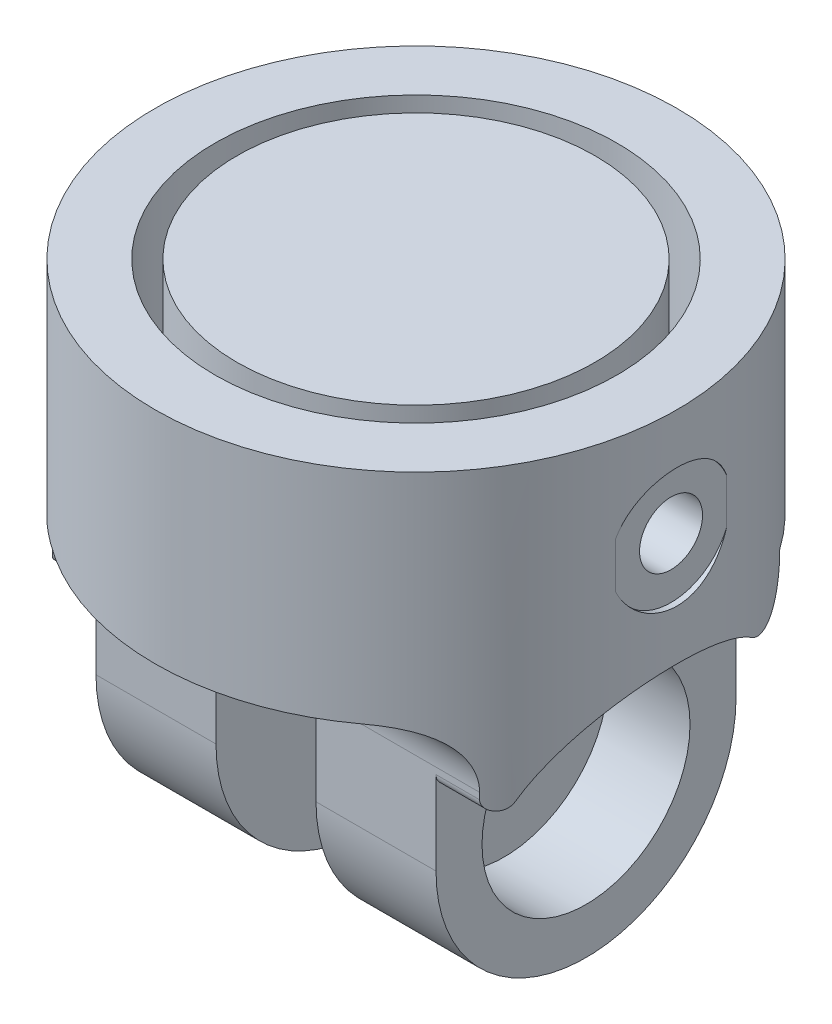
SolidWorks part; units mm, degrees
material "PLA Black"
ref_plane "Front" through (0, 0, 0) normal (0, 0, 1) x (1, 0, 0)
ref_plane "Top" through (0, 0, 0) normal (0, 1, 0) x (1, 0, 0)
ref_plane "Right" through (0, 0, 0) normal (1, 0, 0) x (0, 0, -1)
sketch "Sketch1" plane through (0, 0, 0) normal (0, 1, 0) x (1, 0, 0)
  line L0 (0, 8.95) -> (0, 10.05) construction
  circle A0 centre (0, 0) radius 10.05
  circle A1 centre (0, 0) radius 13.05
  circle A2 centre (0, 0) radius 9.5 construction
  circle A4 centre (0, 0) radius 8.95
  point P11 (0, 9.5)
  dimension "D1" = 1.1
  dimension "D2" = 3
  dimension "D3" = 19
extrude "Boss-Extrude1" add sketch "Sketch1" along normal blind 10 contours A1 A0 | A4 region at (-12.6809, 0, 0) region at (0, 0, 0)
sketch "Sketch3" plane through (0, 0, 0) normal (0, -1, 0) x (1, 0, 0)
  circle A2 centre (0, 0) radius 13.05 construction
  circle A3 centre (0, 0) radius 13.05
extrude "Boss-Extrude2" add sketch "Sketch3" along normal blind 1
sketch "Sketch4" plane through (0, -1, 0) normal (0, -1, 0) x (1, 0, 0)
  line L0 (0, 17.8908) -> (0, -17.0763) construction
  line L1 (2.5, 7.5) -> (8.5, 7.5)
  line L2 (2.5, 7.5) -> (2.5, -7.5)
  line L3 (2.5, -7.5) -> (8.5, -7.5)
  line L4 (8.5, 7.5) -> (8.5, -7.5)
  line L5 (-8.5, 7.5) -> (-8.5, -7.5)
  line L6 (-2.5, -7.5) -> (-8.5, -7.5)
  line L7 (-2.5, 7.5) -> (-2.5, -7.5)
  line L8 (-2.5, 7.5) -> (-8.5, 7.5)
  line L9 (16.8049, 0) -> (-19.8998, 0) construction
  dimension "D1" = 6
  dimension "D2" = 5
  dimension "D3" = 15
extrude "Boss-Extrude3" add sketch "Sketch4" along normal blind 15
sketch "Sketch5" plane through (8.5, 0, 0) normal (1, 0, 0) x (0, 0, -1)
  line L0 (-7.5, -16) -> (-7.5, -1) construction
  line L1 (7.5, -16) -> (7.5, -1) construction
  line L2 (7.5, -8.5) -> (7.5, -17.1619)
  line L3 (7.5, -17.1619) -> (-7.5, -17.1619)
  line L4 (-7.5, -17.1619) -> (-7.5, -8.5)
  arc A0 (-7.5, -8.5) -> (7.5, -8.5) centre (0, -8.5) ccw
  circle A1 centre (0, -8.5) radius 1.55
  dimension "D1" = 3.1
extrude "Cut-Extrude1" cut sketch "Sketch5" against normal through all both and the other way through all
sketch "Sketch6" plane through (8.5, 0, 0) normal (1, 0, 0) x (0, 0, -1)
  circle A0 centre (0, -8.5) radius 5.2
  dimension "D1" = 10.4
extrude "Cut-Extrude2" cut sketch "Sketch6" against normal blind 4.1
mirror "Mirror1" about plane through (0, 0, 0) normal (1, 0, 0) of "Cut-Extrude2"
ref_plane "Plane9" through (1.335, 0, 0) normal (1, 0, 0) x (0, 0, -1)
sketch "Sketch7" plane through (1.335, 0, 0) normal (1, 0, 0) x (0, 0, -1)
  line L0 (3.555, -8.5) -> (3.555, -1) construction
  line L1 (7.5, -1) -> (-7.5, -1) construction
  line L2 (3.4474, -7.632) -> (1.7775, -1) construction
  line L3 (3.1303, -6.8149) -> (0, -1) construction
  line L4 (1.7775, -0.6757) -> (1.7775, -1.4422) construction
  line L5 (2.6911, -6.1771) -> (-1.7775, -1) construction
  line L6 (2.2506, -5.7481) -> (-3.555, -1) construction
  line L8 (0, -1.6788) -> (0, 0) construction
  line L9 (-8.4824, -8.5) -> (8.712, -8.5) construction
  line L10 (1.8766, -5.4807) -> (-5.3325, -1) construction
  line L11 (-3.555, -0.3587) -> (-3.555, -1.6788) construction
  circle A0 centre (0, -8.5) radius 3.555 construction
  dimension "D1" = 7.11
  dimension "D2" = 31.862
  dimension "D3" = 7.5
ref_plane "Plane1" through (1.335, -1, -3.555) normal (0, 1, 0) x (1, 0, 0)
ref_plane "Plane2" through (1.335, -1, -1.7775) normal (0, 0.9697, 0.2442) x (1, 0, 0)
ref_plane "Plane3" through (1.335, -1, 0) normal (0, 0.8805, 0.474) x (1, 0, 0)
ref_plane "Plane5" through (1.335, -1, 1.7775) normal (0, 0.757, 0.6534) x (1, 0, 0)
ref_plane "Plane6" through (1.335, -1, 3.555) normal (0, 0.6331, 0.7741) x (1, 0, 0)
ref_plane "Plane7" through (1.335, -1, 5.3325) normal (0, 0.5279, 0.8493) x (1, 0, 0)
sketch "Sketch8" plane through (1.335, -1, -3.555) normal (0, 1, 0) x (1, 0, 0)
  circle A0 centre (0, 0) radius 0.4895
  dimension "D1" = 0.979
extrude "Cut-Extrude5" cut sketch "Sketch8" along normal blind 5.5 and the other way through all
sketch "Sketch9" plane through (1.335, -1, -1.7775) normal (0, 0.9697, 0.2442) x (1, 0, 0)
  circle A0 centre (0, 0) radius 0.4895
  dimension "D1" = 0.979
extrude "Cut-Extrude3" cut sketch "Sketch9" along normal blind 5.5
sketch "Sketch10" plane through (1.335, -1, 0) normal (0, 0.8805, 0.474) x (1, 0, 0)
  circle A0 centre (0, 0) radius 0.4895
  dimension "D1" = 0.979
sketch "Sketch11" plane through (1.335, -1, 1.7775) normal (0, 0.757, 0.6534) x (1, 0, 0)
  circle A0 centre (0, 0) radius 0.4895
  dimension "D1" = 0.979
sketch "Sketch12" plane through (1.335, -1, 3.555) normal (0, 0.6331, 0.7741) x (1, 0, 0)
  circle A0 centre (0, 0) radius 0.4895
  dimension "D1" = 0.979
sketch "Sketch14" plane through (1.335, -1, 5.3325) normal (0, 0.5279, 0.8493) x (1, 0, 0)
  circle A0 centre (0, 0) radius 0.4895
  dimension "D1" = 0.979
extrude "Cut-Extrude6" cut sketch "Sketch10" along normal blind 5.5 and the other way through all
extrude "Cut-Extrude7" cut sketch "Sketch11" along normal blind 5.5 and the other way through all contours A0
extrude "Cut-Extrude8" cut sketch "Sketch12" along normal blind 5.5 and the other way through all contours A0
extrude "Cut-Extrude9" cut sketch "Sketch14" along normal blind 5.5 and the other way through all contours A0
ref_plane "Plane8" through (13.05, 0, 0) normal (1, 0, 0) x (0, 0, -1)
hole_wizard "Tap Drill for M3 Helicoil1" positions "Sketch17" profile "Sketch18" hole size "M3x0.5" standard "DIN"
sketch "Sketch17" plane through (13.05, 0, 0) normal (1, 0, 0) x (0, 0, -1)
  line L0 (-22.2973, 4.5) -> (18.0703, 4.5) construction
  line L2 (13.05, 10) -> (-13.05, 10) construction
  line L3 (-13.05, -1) -> (13.05, -1) construction
  line L4 (0, 12.2732) -> (0, -5.3405) construction
  line L6 (-7.5, -8.5) -> (-7.5, -1) construction
  line L7 (7.5, -8.5) -> (7.5, -1) construction
  point P0 (0, 4.5)
sketch "Sketch18" plane through (13.05, 4.5, 0) normal (0, 1, 0) x (0, 0, -1)
  line L0 (0, 0) -> (0, 6.9464)
  line L1 (0, 6.9464) -> (1.575, 6)
  line L2 (1.575, 6) -> (1.575, 0)
  line L5 (1.575, 0) -> (0, 0)
  line L10 (0, 6.9464) -> (-1.575, 6) construction
  line L11 (0, -6.35) -> (0, 107.95) construction
  dimension "Hole Dia." = 3.15
  dimension "Hole Depth" = 6
  dimension "Drill Angle" = 118
sketch "Sketch20" plane through (13.05, 0, 0) normal (1, 0, 0) x (0, 0, -1)
  circle A0 centre (0, 4.5) radius 3
  dimension "D1" = 6
extrude "Cut-Extrude10" cut sketch "Sketch20" against normal blind 0.3
sketch "Sketch21" plane through (8.5, 0, 0) normal (1, 0, 0) x (0, 0, -1)
  line L0 (7.5, -1) -> (-7.5, -1) construction
  line L1 (7.5, -0.1252) -> (7.5, -1.1767)
  line L2 (0.9244, -19.0662) -> (-4.8209, -14.2453) construction
  line L3 (0, 5.2718) -> (0, -9.2894) construction
  line L4 (0, 10) -> (0, -1) construction
  line L5 (-7.5, -0.1252) -> (-7.5, -4.3226)
  line L6 (7.5, -0.1252) -> (-7.5, -0.1252)
  line L7 (-7.5, -8.5) -> (-7.5, -1) construction
  line L8 (7.5, -8.5) -> (7.5, -1) construction
  line L9 (0, -1) -> (9.4693, -4.4465) construction
  line L10 (0, -1) -> (1.6171, -0.0664) construction
  line L11 (4.6128, -2.5863) -> (7.5, -1.1767) construction
  line L12 (10.5662, -7.5756) -> (4.8209, -2.7547) construction
  line L13 (-4.8209, -14.2453) -> (4.8209, -2.7547) construction
  line L14 (10.5662, -7.5756) -> (0.9244, -19.0662) construction
  arc A0 (-6.4204, -4.6233) -> (4.6128, -2.5863) centre (0, -8.5) cw
  arc A1 (-6.4204, -4.6233) -> (-7.5, -4.3226) centre (-6.9183, -4.3226) cw
  arc A2 (7.5, -1.1767) -> (4.6128, -2.5863) centre (5.7123, -1.1767) cw
  circle A3 centre (0, -8.5) radius 1.55 construction
  arc A4 (-4.8209, -14.2453) -> (4.8209, -2.7547) centre (0, -8.5) cw construction
  dimension "D1" = 30
  dimension "D3" = 7.5
  dimension "D2" = 50
  dimension "D4" = 15
extrude "Boss-Extrude4" add sketch "Sketch21" along normal up to surface (2.1795 mm away) up to face at (12.895, 4.5, 0)
mirror "Mirror2" about plane through (0, 0, 0) normal (1, 0, 0) of "Boss-Extrude4", "Tap Drill for M3 Helicoil1", "Cut-Extrude10"
fillet "Fillet1" radius 3 2 edges at (-6.5898, -1, 7.5) (6.5898, -1, 7.5)
equation "\"knee_angle\"= 70"
equation "\"ankle_angle\" = 120"
equation "\"hip_angle\" = 30"
equation "\"spring_ankle_parallel_arm_diameter\"= 0.89"
equation "\"spring_ankle_parallel_arm_length\"= 13"
equation "\"spring_ankle_parallel_intern_diameter\"= 6.22"
equation "\"spring_ankle_parallel_angle\"= \"ankle_angle\""
equation "\"spring_ankle_parallel_turns\"= 3"
equation "\"spring_ankle_parallel_pitch\"= \"spring_ankle_parallel_arm_diameter\" * 1.01"
equation "\"spring_ankle_parallel_cutting_distance\"= (1-\"spring_ankle_parallel_angle\" / 360) * \"spring_ankle_parallel_pitch\""
equation "\"spring_ankle_serial_arm_diameter\"= 0.89"
equation "\"spring_ankle_serial_arm_length\"= 10"
equation "\"spring_ankle_serial_intern_diameter\"= 6.22"
equation "\"spring_ankle_serial_angle\"= \"90\""
equation "\"spring_ankle_serial_turns\"= 3"
equation "\"spring_ankle_serial_pitch\"= \"spring_ankle_serial_arm_diameter\" * 1.01"
equation "\"spring_ankle_serial_cutting_distance\"= (1-\"spring_ankle_serial_angle\" / 360) * \"spring_ankle_serial_pitch\""
equation "\"spring_knee_parallel_arm_diameter\"= 0.43"
equation "\"spring_knee_parallel_arm_length\"= 15"
equation "\"spring_knee_parallel_intern_diameter\"= 5.46"
equation "\"spring_knee_parallel_angle\"= \"knee_angle\""
equation "\"spring_knee_parallel_turns\"= 3"
equation "\"spring_knee_parallel_pitch\"= \"spring_knee_parallel_arm_diameter\" * 1.01"
equation "\"spring_knee_parallel_cutting_distance\"= (1-\"spring_knee_parallel_angle\" / 360) * \"spring_knee_parallel_pitch\""
equation "\"spring_knee_serial_arm_diameter\"= 0.43"
equation "\"spring_knee_serial_arm_length\"= 10"
equation "\"spring_knee_serial_intern_diameter\"= 5.46"
equation "\"spring_knee_serial_angle\"= \"90\""
equation "\"spring_knee_serial_turns\"= 3"
equation "\"spring_knee_serial_pitch\"= \"spring_knee_serial_arm_diameter\" * 1.01"
equation "\"spring_knee_serial_cutting_distance\"= (1-\"spring_knee_serial_angle\" / 360) * \"spring_knee_serial_pitch\""
equation "\"spring_ankle_parallel_nominal_diameter\"= \"spring_ankle_parallel_arm_diameter\" + \"spring_ankle_parallel_intern_diameter\""
equation "\"spring_ankle_serial_nominal_diameter\"= \"spring_ankle_serial_arm_diameter\" + \"spring_ankle_serial_intern_diameter\""
equation "\"spring_knee_parallel_nominal_diameter\"= \"spring_knee_parallel_arm_diameter\" + \"spring_knee_parallel_intern_diameter\""
equation "\"spring_knee_serial_nominal_diameter\"= \"spring_knee_serial_arm_diameter\" + \"spring_knee_serial_intern_diameter\""
equation "\"D1@Sketch7\"=\"spring_ankle_parallel_nominal_diameter\""
equation "\"D1@Sketch8\"=\"spring_ankle_parallel_arm_diameter\"*1.1"
equation "\"D1@Sketch9\"=\"spring_ankle_parallel_arm_diameter\"*1.1"
equation "\"D1@Sketch10\"=\"spring_ankle_parallel_arm_diameter\"*1.1"
equation "\"D1@Sketch11\"=\"spring_ankle_parallel_arm_diameter\"*1.1"
equation "\"D1@Sketch12\"=\"spring_ankle_parallel_arm_diameter\"*1.1"
equation "\"D1@Sketch14\"=\"spring_ankle_parallel_arm_diameter\"*1.1"
equation "\"D1@Cut-Extrude3\"=\"spring_ankle_parallel_arm_length\"-\"axis_structure_distance\""
equation "\"axis_structure_distance\"= 7.5"
equation "\"D1@Cut-Extrude5\"=\"spring_ankle_parallel_arm_length\"-\"axis_structure_distance\""
equation "\"D1@Cut-Extrude6\"=\"spring_ankle_parallel_arm_length\"-\"axis_structure_distance\""
equation "\"D1@Cut-Extrude7\"=\"spring_ankle_parallel_arm_length\"-\"axis_structure_distance\""
equation "\"D1@Cut-Extrude8\"=\"spring_ankle_parallel_arm_length\"-\"axis_structure_distance\""
equation "\"D1@Cut-Extrude9\"=\"spring_ankle_parallel_arm_length\"-\"axis_structure_distance\""
equation "\"D1@Boss-Extrude3\"=\"axis_structure_distance\"*2"
equation "\"ankle_angle_max\" = 120"
equation "\"ankle_angle_min\" = 50"
equation "\"knee_angle_max\" = 120"
equation "\"knee_angle_min\" = 0"
equation "\"hip_angle_max\" = 45"
equation "\"hip_angle_min\" = -45"
equation "\"D1@Sketch21\"=\"ankle_angle_max\"-90"
equation "\"D2@Sketch21\"=\"ankle_angle_min\""
equation "\"D1@Plane9\"=(\"spring_ankle_parallel_arm_diameter\"*\"spring_ankle_parallel_turns\")/2"
